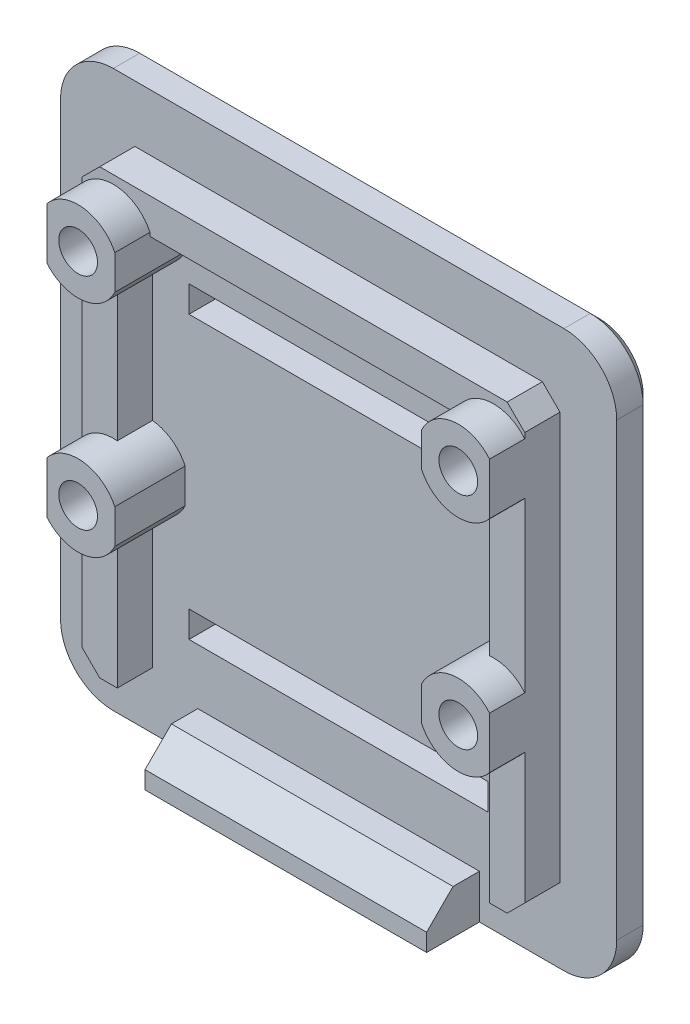
SolidWorks part; units mm, degrees
ref_plane "Front Plane" through (0, 0, 0) normal (0, 0, 1) x (1, 0, 0)
ref_plane "Top Plane" through (0, 0, 0) normal (0, 1, 0) x (1, 0, 0)
ref_plane "Right Plane" through (0, 0, 0) normal (1, 0, 0) x (0, 0, -1)
sketch "Sketch2" plane through (0, 0, 0) normal (0, 0, 1) x (1, 0, 0)
  line L1 (15.8, 15.8) -> (-15.8, 15.8)
  line L2 (15.8, 15.8) -> (15.8, -15.8)
  line L3 (15.8, -15.8) -> (-15.8, -15.8)
  line L4 (-15.8, 15.8) -> (-15.8, -15.8)
  line L5 (15.8, 15.8) -> (-15.8, -15.8) construction
  line L6 (15.8, -15.8) -> (-15.8, 15.8) construction
  point P0 (0, 0)
  dimension "D1" = 31.6
extrude "Boss-Extrude1" add sketch "Sketch2" along normal blind 2 separate body
fillet "Fillet1" radius 3 4 edges at (15.8, 15.8, 1) (15.8, -15.8, 1) (-15.8, -15.8, 1) (-15.8, 15.8, 1)
sketch "Sketch5" plane through (0, 0, 2) normal (0, 0, 1) x (1, 0, 0)
  line L0 (-10.575, -12.575) -> (-10.575, 10.575)
  line L1 (12.575, -12.575) -> (10.575, -12.575)
  line L2 (12.575, -12.575) -> (12.575, 12.575)
  line L3 (12.575, 12.575) -> (-12.575, 12.575)
  line L4 (-12.575, -12.575) -> (-12.575, 12.575)
  line L5 (12.575, -12.575) -> (-12.575, 12.575) construction
  line L6 (12.575, 12.575) -> (-12.575, -12.575) construction
  line L7 (-10.575, 10.575) -> (10.575, 10.575)
  line L8 (10.575, 10.575) -> (10.575, -12.575)
  line L9 (-10.575, -12.575) -> (-12.575, -12.575)
  point P0 (0, 0)
  dimension "D1" = 25.15
  dimension "D2" = 2
  dimension "D3" = 2
extrude "Boss-Extrude2" add sketch "Sketch5" along normal blind 2
chamfer "Chamfer1" distance 1 angle 45 4 edges at (-12.575, 12.575, 3) (12.575, 12.575, 3) (12.575, -12.575, 3) (-12.575, -12.575, 3)
sketch "Sketch6" plane through (0, 0, 2) normal (0, 0, 1) x (1, 0, 0)
  line L0 (-12.8, -15.8) -> (12.8, -15.8) construction
  line L1 (-8, -13.3) -> (8, -13.3)
  line L2 (-8, -13.3) -> (-8, -15.8)
  line L3 (-8, -15.8) -> (8, -15.8)
  line L4 (8, -13.3) -> (8, -15.8)
  line L5 (-8, -13.3) -> (8, -15.8) construction
  line L6 (-8, -15.8) -> (8, -13.3) construction
  point P0 (0, -14.55)
  dimension "D1" = 16
  dimension "D2" = 2.5
extrude "Boss-Extrude3" add sketch "Sketch6" along normal blind 3
sketch "Sketch7" plane through (0, 0, 2) normal (0, 0, 1) x (1, 0, 0)
  line L0 (12.575, -4.1627) -> (12.575, -1.2373)
  line L1 (-12.575, 11.575) -> (-12.575, -11.575) construction
  line L2 (-12.575, -1.2373) -> (-12.575, -4.1627)
  line L3 (-12.575, 11.2627) -> (-12.575, 8.3373)
  line L4 (12.575, 8.3373) -> (12.575, 11.2627)
  line L5 (8.7175, 8.8237) -> (8.7175, 10.7763)
  line L6 (8.7175, -3.6763) -> (8.7175, -1.7237)
  line L7 (-8.7175, 8.8237) -> (-8.7175, 10.7763)
  line L8 (-8.7175, -3.6763) -> (-8.7175, -1.7237)
  arc A0 (12.575, -1.2373) -> (8.7175, -1.7237) centre (10.8, -2.7) ccw
  arc A1 (-12.575, -4.1627) -> (-8.7175, -3.6763) centre (-10.8, -2.7) ccw
  arc A2 (-12.575, 8.3373) -> (-8.7175, 8.8237) centre (-10.8, 9.8) ccw
  arc A3 (12.575, 11.2627) -> (8.7175, 10.7763) centre (10.8, 9.8) ccw
  arc A4 (8.7175, -3.6763) -> (12.575, -4.1627) centre (10.8, -2.7) ccw
  arc A5 (8.7175, 8.8237) -> (12.575, 8.3373) centre (10.8, 9.8) ccw
  arc A6 (-8.7175, 10.7763) -> (-12.575, 11.2627) centre (-10.8, 9.8) ccw
  arc A7 (-8.7175, -1.7237) -> (-12.575, -1.2373) centre (-10.8, -2.7) ccw
  point P11 (0, 0)
  point P14 (0, 0)
  point P20 (-8.6962, 8.8704)
  point P23 (8.7175, 8.8704)
  point P24 (-12.575, -1.2373)
  dimension "D1" = 4.6
extrude "Boss-Extrude4" add sketch "Sketch7" along normal blind 4
sketch "Sketch8" plane through (0, 0, 6) normal (0, 0, 1) x (1, 0, 0)
  circle A0 centre (10.8, -2.7) radius 1.1
  circle A1 centre (-10.8, -2.7) radius 1.1
  circle A2 centre (-10.8, 9.8) radius 1.1
  circle A3 centre (10.8, 9.8) radius 1.1
extrude "Cut-Extrude1" cut sketch "Sketch8" against normal blind 8
sketch "Sketch9" plane through (0, 0, 0) normal (0, 0, -1) x (-1, 0, 0)
  circle A0 centre (10.8, -2.7) radius 2.25
  circle A1 centre (-10.8, -2.7) radius 2.25
  circle A2 centre (-10.8, 9.8) radius 2.25
  circle A3 centre (10.8, 9.8) radius 2.25
  dimension "D1" = 4.5
extrude "Cut-Extrude2" cut sketch "Sketch9" against normal blind 1
sketch "Sketch10" plane through (0, 0, 2) normal (0, 0, 1) x (1, 0, 0)
  line L1 (8.5, -8.6455) -> (-8.5, -8.6455)
  line L2 (8.5, -8.6455) -> (8.5, -10.1455)
  line L3 (8.5, -10.1455) -> (-8.5, -10.1455)
  line L4 (-8.5, -8.6455) -> (-8.5, -10.1455)
  line L5 (8.5, -8.6455) -> (-8.5, -10.1455) construction
  line L6 (8.5, -10.1455) -> (-8.5, -8.6455) construction
  line L7 (8.5, 7.3545) -> (-8.5, 7.3545)
  line L8 (8.5, 7.3545) -> (8.5, 5.8545)
  line L9 (8.5, 5.8545) -> (-8.5, 5.8545)
  line L10 (-8.5, 7.3545) -> (-8.5, 5.8545)
  line L11 (8.5, 7.3545) -> (-8.5, 5.8545) construction
  line L12 (8.5, 5.8545) -> (-8.5, 7.3545) construction
  point P0 (0, -9.3955)
  point P5 (0, 6.6045)
  point P10 (0, 0)
  point P11 (0, 6.7303)
  dimension "D1" = 17
  dimension "D2" = 1.5
  dimension "D3" = 16
extrude "Cut-Extrude3" cut sketch "Sketch10" against normal blind 5
chamfer "Chamfer2" distance 0.5 angle 45 20 edges at (14.9213, -14.9213, 0) (0, -15.8, 0) (15.8, 0, 0) (-14.9213, -14.9213, 0) (14.9213, 14.9213, 0) (-15.8, 0, 0) (0, 15.8, 0) (-14.9213, 14.9213, 0) (-13.05, -2.7, 0) (-13.05, 9.8, 0) (8.55, 9.8, 0) (8.55, -2.7, 0) (8.5, -9.3955, 0) (0, -10.1455, 0) (0, -8.6455, 0) (-8.5, -9.3955, 0) (-8.5, 6.6045, 0) (0, 5.8545, 0) (8.5, 6.6045, 0) (0, 7.3545, 0)
chamfer "Chamfer3" distance 1.5 angle 45 1 edges at (0, -13.3, 5)
